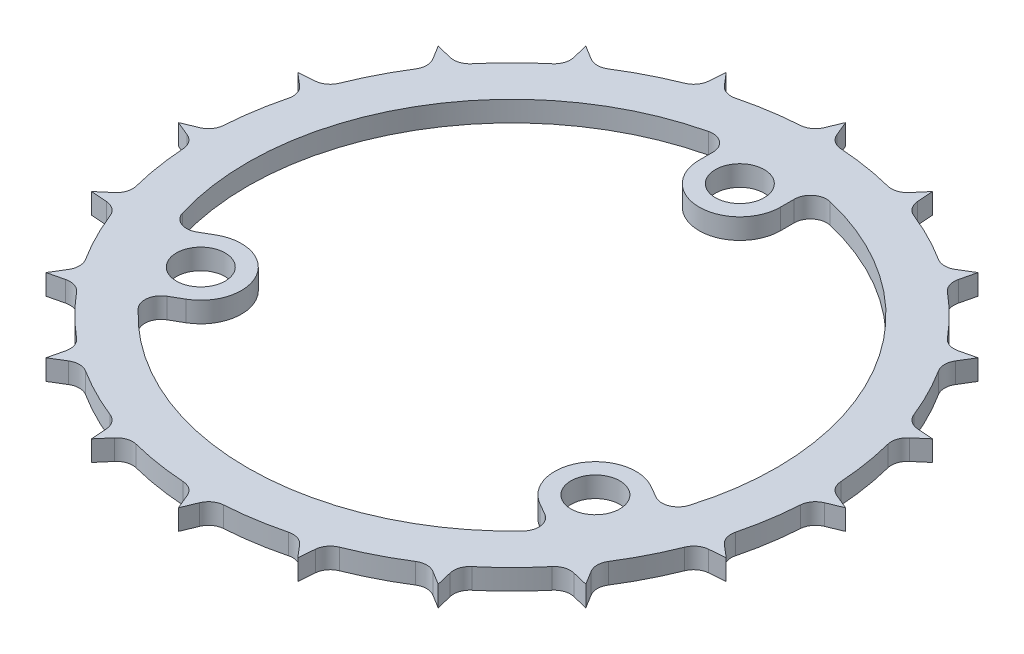
SolidWorks part; units mm, degrees
material "Titanium Ti-8Al-1Mo-1V"
ref_plane "Front Plane" through (0, 0, 0) normal (0, 0, 1) x (1, 0, 0)
ref_plane "Top Plane" through (0, 0, 0) normal (0, 1, 0) x (1, 0, 0)
ref_plane "Right Plane" through (0, 0, 0) normal (1, 0, 0) x (0, 0, -1)
other "Bounding Box"
ref_plane "Default Plane" through (13.8565, 3.175, 6.7999) normal (0, -1, 0) x (-1, 0, 0)
sketch "Sketch1" plane through (0, 0, 0) normal (0, 1, 0) x (1, 0, 0)
  circle A0 centre (0, 0) radius 24.13
  dimension "D1" = 48.26
extrude "Boss-Extrude1" add sketch "Sketch1" along normal mid plane 1.6002
sketch "Sketch2" plane through (0, 0.8001, 0) normal (0, 1, 0) x (1, 0, 0)
  line L0 (-0.7945, 24.1169) -> (0, 26.035)
  line L1 (0, 26.035) -> (0.7945, 24.1169)
  line L2 (0, 26.035) -> (0, 0) construction
  line L3 (-0.7945, 24.1169) -> (0.7945, 24.1169)
  circle A0 centre (0, 0) radius 24.13 construction
  dimension "D1" = 26.035
  dimension "D2" = 45
extrude "Boss-Extrude2" add sketch "Sketch2" against normal through all
fillet "Fillet1" radius 1.27 2 edges at (0.7945, 0, -24.1169) (-0.7945, 0, -24.1169)
pattern_circular "CirPattern1" count 20 over 360 about axis through (0, 0.8001, 0) along (0, -1, 0) of "Fillet1", "Boss-Extrude2" reverse direction yes
sketch "Sketch3" plane through (0, 0.8001, 0) normal (0, 1, 0) x (1, 0, 0)
  circle A0 centre (0, 0) radius 20.6375
  dimension "D1" = 41.275
extrude "Cut-Extrude1" cut sketch "Sketch3" against normal through all
sketch "Sketch4" plane through (0, 0.8001, 0) normal (0, 1, 0) x (1, 0, 0)
  line L0 (-3.175, 17.78) -> (-3.175, 20.3918)
  line L1 (3.175, 17.78) -> (3.175, 20.3918)
  line L2 (0, 0) -> (0, 17.78) construction
  circle A0 centre (0, 17.78) radius 1.905
  arc A1 (-3.175, 17.78) -> (3.175, 17.78) centre (0, 17.78) ccw
  circle A2 centre (0, 0) radius 20.6375 construction
  arc A3 (-3.175, 20.3918) -> (3.175, 20.3918) centre (0, 0) cw
  arc A4 (3.175, 17.78) -> (-3.175, 17.78) centre (0, 17.78) ccw construction
  dimension "D1" = 3.81
  dimension "D2" = 6.35
  dimension "D3" = 17.78
extrude "Boss-Extrude3" add sketch "Sketch4" against normal through all
fillet "Fillet2" radius 1.27 2 edges at (3.175, 0, -20.3918) (-3.175, 0, -20.3918)
pattern_circular "CirPattern2" count 3 over 360 about axis through (0, 0.8001, 0) along (0, -1, 0) of "Fillet2", "Boss-Extrude3" reverse direction yes
